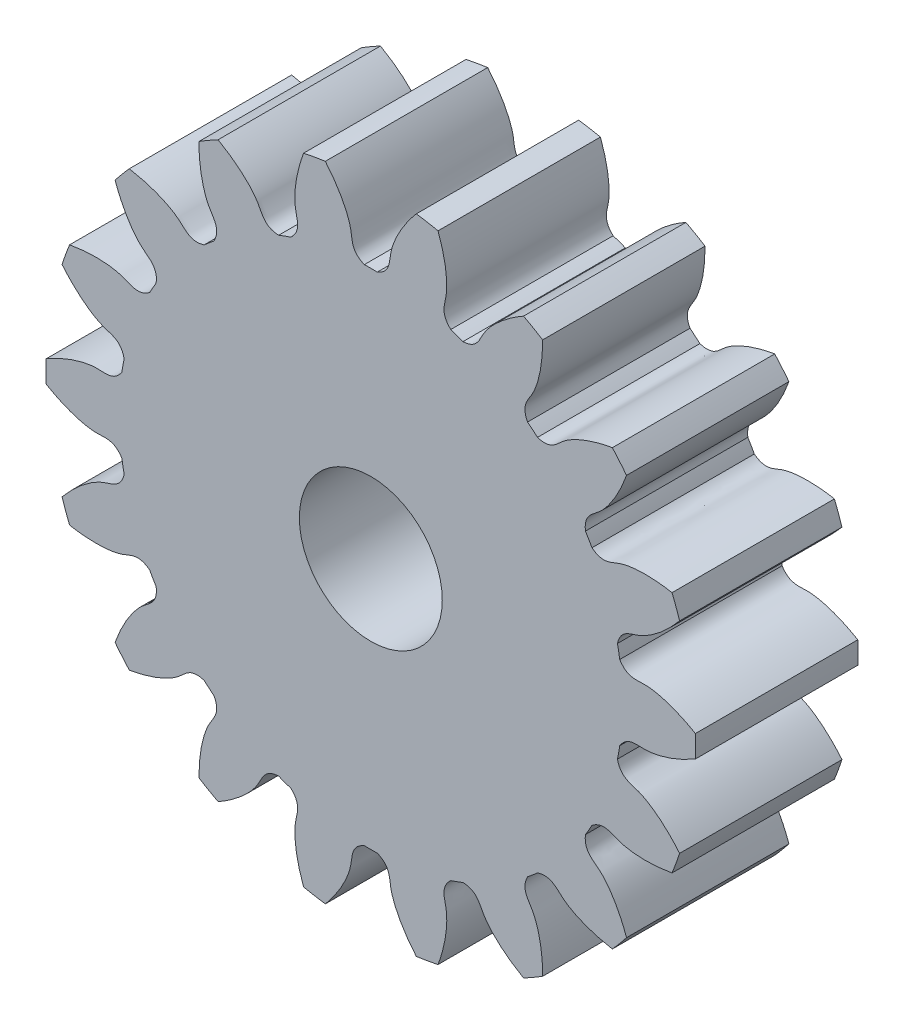
SolidWorks part; units mm, degrees
ref_plane "前视基准面" through (0, 0, 0) normal (0, 0, 1) x (1, 0, 0)
ref_plane "上视基准面" through (0, 0, 0) normal (0, 1, 0) x (1, 0, 0)
ref_plane "右视基准面" through (0, 0, 0) normal (1, 0, 0) x (0, 0, -1)
other "Configuration Table"
sketch "草图1" plane through (0, 0, 0) normal (0, 0, 1) x (1, 0, 0)
  circle A0 centre (0, 0) radius 5
extrude "凸台-拉伸1" add sketch "草图1" along normal blind 2.5
ref_axis "基准轴1" through (0, 0, 2.5) along (0, 0, -1)
sketch "草图2" plane through (0, 0, 0) normal (0, 0, 1) x (1, 0, 0)
  line L0 (0, 0) -> (0, 5) construction
  circle A0 centre (0, 0) radius 5 construction
  arc A1 (0.0997, 3.8737) -> (-0.0997, 3.8737) centre (0, 0) ccw
  arc A2 (1.5493, 5.6533) -> (-1.5493, 5.6533) centre (0, 0) ccw
  spline S0 degree 3 poles (0.0997, 3.8737) (0.3076, 3.9593) (0.2814, 4.1193) (0.3159, 4.2713) (0.3194, 4.2853) (0.3236, 4.3008) (0.3285, 4.3178) (0.3343, 4.3364) (0.341, 4.3564) (0.3487, 4.378) (0.3574, 4.4009) (0.3672, 4.4252) (0.3781, 4.4509) (0.3903, 4.4779) (0.4037, 4.5062) (0.4184, 4.5357) (0.4345, 4.5664) (0.452, 4.5982) (0.471, 4.6312) (0.4916, 4.6653) (0.5137, 4.7003) (0.5374, 4.7363) (0.5628, 4.7733) (0.5899, 4.8111) (0.6188, 4.8496) (0.6495, 4.889) (0.6821, 4.929) (0.7165, 4.9697) (0.7529, 5.0109) (0.7912, 5.0527) (0.8315, 5.0949) (0.8738, 5.1374) (0.9182, 5.1803) (0.9647, 5.2235) (1.0133, 5.2668) (1.0641, 5.3103) (1.117, 5.3538) (1.1721, 5.3973) (1.2294, 5.4407) (1.289, 5.4839) (1.3507, 5.527) (1.437, 5.5845) (1.5038, 5.6262) (1.5493, 5.6533) knots 0 0 0 0 0.187592 0.192996 0.199121 0.205966 0.213531 0.221818 0.230824 0.240552 0.250999 0.262168 0.274057 0.286666 0.299996 0.314047 0.328818 0.344309 0.360521 0.377454 0.395107 0.413481 0.432575 0.45239 0.472926 0.494181 0.516158 0.538855 0.562272 0.58641 0.611269 0.636848 0.663148 0.690168 0.717909 0.74637 0.775552 0.805454 0.836077 0.867421 0.899485 0.932269 1 1 1 1
  spline S1 degree 3 poles (-0.0997, 3.8737) (-0.3076, 3.9593) (-0.2814, 4.1193) (-0.3159, 4.2713) (-0.3194, 4.2853) (-0.3236, 4.3008) (-0.3285, 4.3178) (-0.3343, 4.3364) (-0.341, 4.3564) (-0.3487, 4.378) (-0.3574, 4.4009) (-0.3672, 4.4252) (-0.3781, 4.4509) (-0.3903, 4.4779) (-0.4037, 4.5062) (-0.4184, 4.5357) (-0.4345, 4.5664) (-0.452, 4.5982) (-0.471, 4.6312) (-0.4916, 4.6653) (-0.5137, 4.7003) (-0.5374, 4.7363) (-0.5628, 4.7733) (-0.5899, 4.8111) (-0.6188, 4.8496) (-0.6495, 4.889) (-0.6821, 4.929) (-0.7165, 4.9697) (-0.7529, 5.0109) (-0.7912, 5.0527) (-0.8315, 5.0949) (-0.8738, 5.1374) (-0.9182, 5.1803) (-0.9647, 5.2235) (-1.0133, 5.2668) (-1.0641, 5.3103) (-1.117, 5.3538) (-1.1721, 5.3973) (-1.2294, 5.4407) (-1.289, 5.4839) (-1.3507, 5.527) (-1.437, 5.5845) (-1.5038, 5.6262) (-1.5493, 5.6533) knots 0 0 0 0 0.187592 0.192996 0.199121 0.205966 0.213531 0.221818 0.230824 0.240552 0.250999 0.262168 0.274057 0.286666 0.299996 0.314047 0.328818 0.344309 0.360521 0.377454 0.395107 0.413481 0.432575 0.45239 0.472926 0.494181 0.516158 0.538855 0.562272 0.58641 0.611269 0.636848 0.663148 0.690168 0.717909 0.74637 0.775552 0.805454 0.836077 0.867421 0.899485 0.932269 1 1 1 1
extrude "切除-拉伸1" cut sketch "草图2" along normal through all
pattern_circular "阵列(圆周)1" count 18 every 20 about axis through (0, 0, 2.5) along (0, 0, -1) of "切除-拉伸1"
sketch "草图3" plane through (0, 0, 0) normal (0, 0, 1) x (1, 0, 0)
  circle A0 centre (0, 0) radius 4.5 construction
  dimension "Dn" = 9
sketch "草图4" plane through (0, 0, 0) normal (0, 0, -1) x (-1, 0, 0)
  circle A0 centre (0, 0) radius 1.1
  dimension "D1" = 2.2
extrude "切除-拉伸2" cut sketch "草图4" against normal up to next
